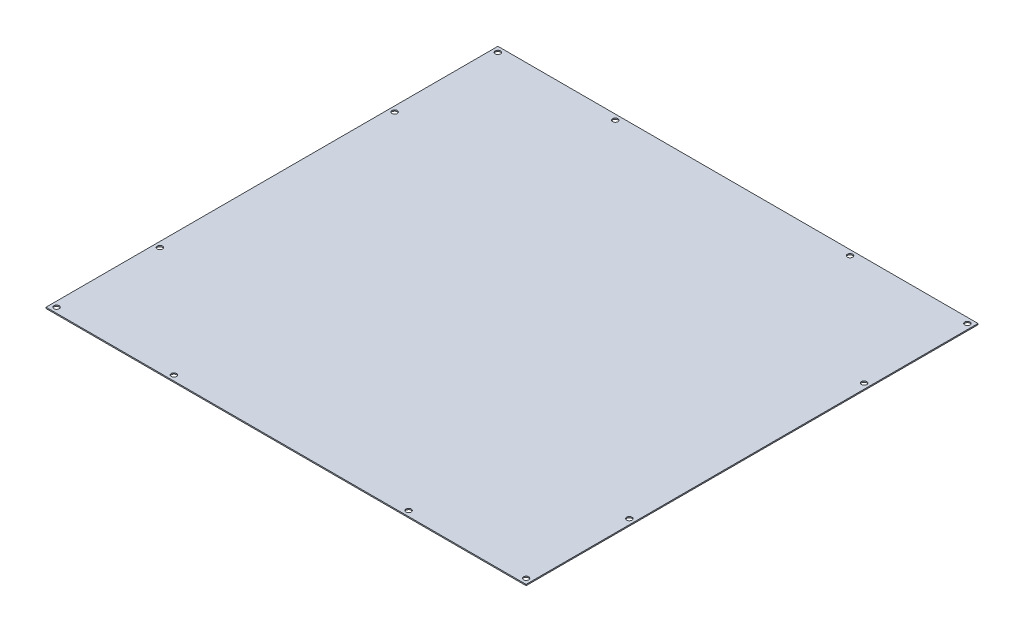
SolidWorks part; units mm, degrees
ref_plane "Front Plane" through (0, 0, 0) normal (0, 0, 1) x (1, 0, 0)
ref_plane "Top Plane" through (0, 0, 0) normal (0, 1, 0) x (1, 0, 0)
ref_plane "Right Plane" through (0, 0, 0) normal (1, 0, 0) x (0, 0, -1)
sketch "Sketch1" plane through (0, 0, 0) normal (0, 1, 0) x (1, 0, 0)
  line L1 (-204.5, -192.5) -> (204.5, -192.5)
  line L2 (-204.5, -192.5) -> (-204.5, 192.5)
  line L3 (-204.5, 192.5) -> (204.5, 192.5)
  line L4 (204.5, -192.5) -> (204.5, 192.5)
  line L5 (-204.5, -192.5) -> (204.5, 192.5) construction
  line L6 (-204.5, 192.5) -> (204.5, -192.5) construction
  point P0 (0, 0)
  dimension "D1" = 409
  dimension "D2" = 385
extrude "Boss-Extrude1" add sketch "Sketch1" along normal blind 1
hole_wizard "M4 Clearance Hole1" positions "Sketch2" profile "Sketch4" hole size "M4" standard "ANSI Metric" end condition through all
sketch "Sketch2" plane through (0, 1, 0) normal (0, 1, 0) x (1, 0, 0)
  line L0 (204.5, 192.5) -> (-204.5, 192.5) construction
  line L1 (-204.5, 192.5) -> (-204.5, -192.5) construction
  line L2 (-200, 100) -> (-200, -100)
  line L3 (0, -55) -> (0, 55) construction
  line L4 (200, 100) -> (200, -100)
  line L5 (-100, 188) -> (100, 188)
  line L6 (-55, 0) -> (55, 0) construction
  line L7 (-100, -188) -> (100, -188)
  point P0 (-200, 188)
  point P7 (-200, 100)
  point P8 (-200, -100)
  point P10 (-200, 0)
  point P21 (200, -100)
  point P22 (200, 100)
  point P23 (200, 188)
  point P24 (-100, 188)
  point P25 (100, 188)
  point P33 (0, 188)
  point P38 (100, -188)
  point P39 (-100, -188)
  point P40 (200, -188)
  point P41 (-200, -188)
  dimension "D1" = 4.5
  dimension "D2" = 4.5
  dimension "D3" = 200
  dimension "D4" = 200
sketch "Sketch4" plane through (-200, 1, -188) normal (1, 0, 0) x (0, 0, 1)
  line L0 (0, 0) -> (0, 1)
  line L1 (0, 1) -> (2.25, 1)
  line L2 (2.25, 1) -> (2.25, 0)
  line L5 (2.25, 0) -> (0, 0)
  line L11 (0, -6.35) -> (0, 107.95) construction
  dimension "Thru Hole Dia." = 4.5
  dimension "Thru Hole Depth" = 1
